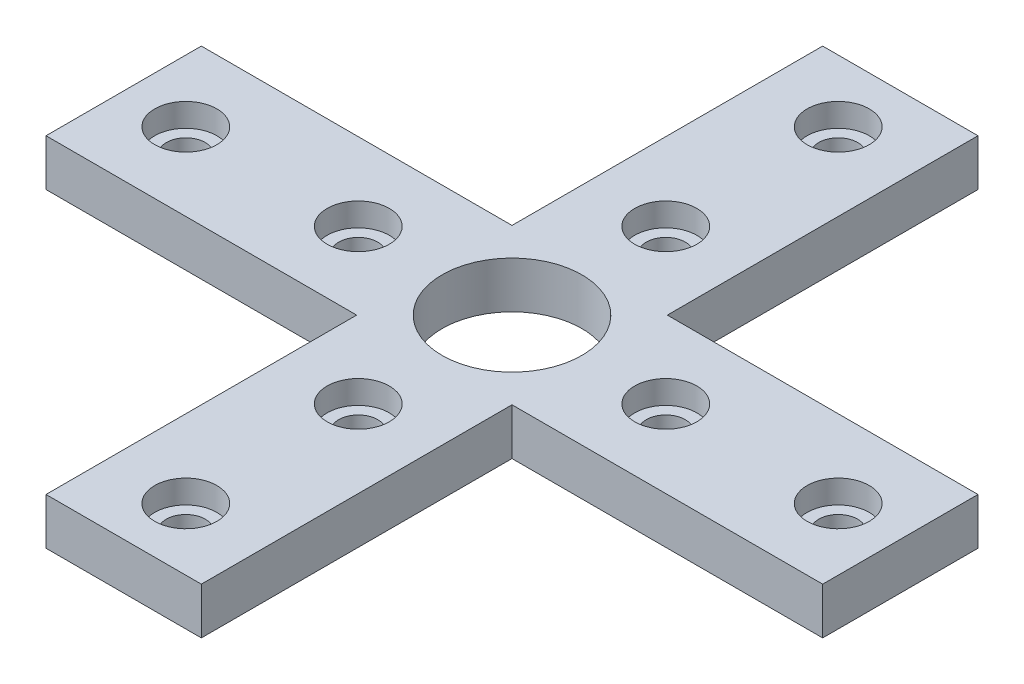
SolidWorks part; units mm, degrees
ref_plane "前视基准面" through (0, 0, 0) normal (0, 0, 1) x (1, 0, 0)
ref_plane "上视基准面" through (0, 0, 0) normal (0, 1, 0) x (1, 0, 0)
ref_plane "右视基准面" through (0, 0, 0) normal (1, 0, 0) x (0, 0, -1)
other "Configuration Table"
sketch "草图1" plane through (0, 0, 0) normal (0, 1, 0) x (1, 0, 0)
  line L1 (-25, -5) -> (25, -5)
  line L2 (-25, -5) -> (-25, 5)
  line L3 (-25, 5) -> (25, 5)
  line L4 (25, -5) -> (25, 5)
  line L5 (-25, -5) -> (25, 5) construction
  line L6 (-25, 5) -> (25, -5) construction
  line L7 (-5, -25) -> (5, -25)
  line L8 (-5, -25) -> (-5, 25)
  line L9 (-5, 25) -> (5, 25)
  line L10 (5, -25) -> (5, 25)
  line L11 (-5, -25) -> (5, 25) construction
  line L12 (-5, 25) -> (5, -25) construction
  circle A18 centre (0, 0) radius 4.5
  dimension "D3" = 50
  dimension "D1" = 10
  dimension "D2" = 9
extrude "凸台-拉伸1" add sketch "草图1" along normal blind 3 contours L1 L8 L3 L2 | L3 L10 L9 L8 | L10 L1 L4 L3 | L7 L10 L1 L8 | L1 L10 L3 L8 A18 region at (-15, 0, 0) region at (-4.8586, 0, 0) region at (0, 0, 15) region at (15, 0, 0) region at (0, 0, -15)
sketch "草图2" plane through (0, 0, 0) normal (0, -1, 0) x (-1, 0, 0)
  line L0 (-25, -5) -> (-25, 5) construction
  circle A0 centre (-9.8995, 0) radius 2
  circle A1 centre (-9.8995, 0) radius 1.25
  circle A2 centre (-21, 0) radius 2
  circle A3 centre (-21, 0) radius 1.25
  point P8 (0, 0)
  dimension "D1" = 4
  dimension "D2" = 2.5
  dimension "D3" = 4
extrude "切除-拉伸1" cut sketch "草图2" against normal through all contours A1 | A3
extrude "切除-拉伸2" cut sketch "草图2<3>" along normal blind 1.5 from surface contours A2 A3 | A0 region at (22.9434, 0, 0) starting at face at (9.8995, 3, -1.25)
sketch "草图2<3>" plane through (0, 0, 0) normal (0, -1, 0) x (-1, 0, 0) same geometry as "草图2"
pattern_circular "阵列(圆周)1" count 4 over 360 about axis through (0, 3, 0) along (0, -1, 0) of "切除-拉伸1", "切除-拉伸2"
